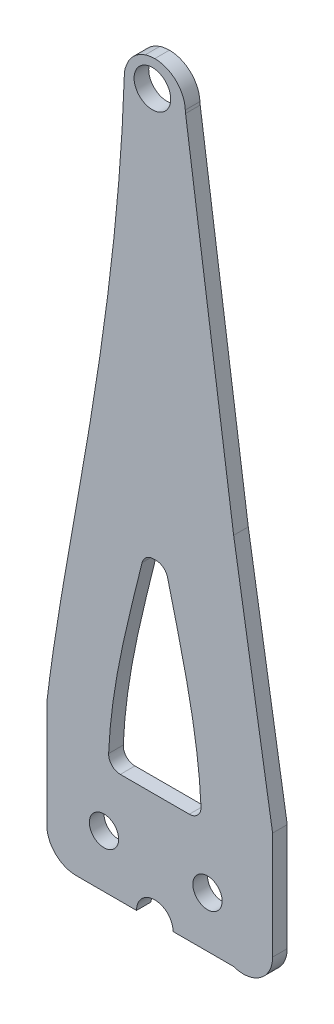
SolidWorks part; units mm, degrees
ref_plane "Front Plane" through (0, 0, 0) normal (0, 0, 1) x (1, 0, 0)
ref_plane "Top Plane" through (0, 0, 0) normal (0, 1, 0) x (1, 0, 0)
ref_plane "Right Plane" through (0, 0, 0) normal (1, 0, 0) x (0, 0, -1)
sketch "Sketch1" plane through (0, 0, 0) normal (0, 0, 1) x (1, 0, 0)
  line L0 (0, 2.6471) -> (0, -62.1483) construction
  line L1 (0, -62.1483) -> (-9.3726, -62.1483) construction
  line L3 (0, -29.7506) -> (-5.9944, -29.7506) construction
  line L4 (-6.8326, -62.1483) -> (6.8326, -62.1483)
  line L5 (-9.3726, -59.6083) -> (-9.3726, -50.4317)
  line L7 (10.218, -59.7531) -> (10.218, -50.4317)
  line L8 (0, -29.7506) -> (6.8398, -29.7506) construction
  line L9 (0, -29.7506) -> (0, -30.7704) construction
  line L13 (2.6678, -0.1469) -> (6.8398, -29.7506)
  line L14 (6.8398, -29.7506) -> (10.218, -50.4317)
  arc A0 (2.645, 0.1059) -> (0, 2.6471) centre (0, 0) ccw
  arc A1 (-2.6008, 0.493) -> (-2.6468, 0.0387) centre (0, 0) ccw
  arc A2 (-0.8377, 2.5111) -> (-2.217, 1.4464) centre (0, 0) ccw
  arc A3 (10.218, -59.7531) -> (6.8326, -62.1483) centre (7.678, -59.7531) cw
  arc A4 (-9.3726, -59.6083) -> (-6.8326, -62.1483) centre (-6.8326, -59.6083) ccw
  arc A5 (-2.6468, 0.0387) -> (-2.648, -0.0092) centre (-5.1866, 0.0758) cw
  arc A6 (2.645, 0.1059) -> (2.6678, -0.1469) centre (5.183, 0.2076) ccw
  spline S0 degree 2 poles (0, 2.6471) (-0.562, 2.6066) (-0.8377, 2.5111) knots 0 0 0 0.007249 0.007249 0.007249
  spline S1 degree 3 poles (-2.217, 1.4464) (-2.3484, 1.2496) (-2.5622, 0.7228) (-2.6008, 0.493) knots 0.022132 0.022132 0.022132 0.022132 0.030911 0.030911 0.030911 0.030911
  spline S2 degree 3 poles (-2.648, -0.0092) (-2.983, -10.0213) (-5.2117, -26.7487) (-8.559, -43.5813) (-9.3726, -50.4317) knots 0.035875 0.035875 0.035875 0.035875 0.412185 0.675163 0.675163 0.675163 0.675163
  point P13 (-9.3726, -48.7371)
  point P27 (2.6471, 0)
  dimension "D1" = 13.4112
  dimension "D2" = 2.54
  dimension "D3" = 2.54
  dimension "D4" = 64.7954
extrude "Boss-Extrude1" add sketch "Sketch1" along normal blind 1.27
sketch "Sketch2" plane through (0, 0, 1.27) normal (0, 0, 1) x (1, 0, 0)
  line L0 (-6.8326, -62.1483) -> (6.8326, -62.1483) construction
  line L1 (-1.5875, -62.1483) -> (1.5875, -62.1483)
  line L8 (6.8398, -29.7506) -> (2.6678, -0.1469)
  line L9 (10.218, -50.4317) -> (6.8398, -29.7506)
  line L10 (10.218, -59.7531) -> (10.218, -50.4317)
  line L11 (0, -52.6291) -> (-2.993, -52.6291)
  line L12 (0, -52.6291) -> (2.993, -52.6291)
  line L13 (0.1175, -35.0015) -> (-0.1175, -35.0015)
  line L14 (-6.8326, -62.1483) -> (6.8326, -62.1483)
  line L15 (-9.3726, -50.4317) -> (-9.3726, -59.6083)
  line L16 (6.8398, -29.7506) -> (2.6678, -0.1469)
  line L17 (10.218, -50.4317) -> (6.8398, -29.7506)
  line L18 (10.218, -59.7531) -> (10.218, -50.4317)
  line L19 (-6.8326, -62.1483) -> (6.8326, -62.1483)
  line L20 (-9.3726, -50.4317) -> (-9.3726, -59.6083)
  arc A1 (1.5875, -62.1483) -> (-1.5875, -62.1483) centre (0, -62.1483) ccw
  arc A6 (-4.0081, -51.5691) -> (-2.993, -52.6291) centre (-2.993, -51.6131) ccw
  arc A7 (4.0081, -51.5691) -> (2.993, -52.6291) centre (2.993, -51.6131) cw
  arc A8 (-1.1039, -35.7742) -> (-0.1175, -35.0015) centre (-0.1175, -36.0175) cw
  arc A9 (1.1039, -35.7742) -> (0.1175, -35.0015) centre (0.1175, -36.0175) ccw
  arc A18 (-0.8377, 2.5111) -> (-2.217, 1.4464) centre (0, 0) ccw
  arc A19 (2.645, 0.1059) -> (0, 2.6471) centre (0, 0) ccw
  arc A20 (2.645, 0.1059) -> (2.6678, -0.1469) centre (5.183, 0.2076) ccw
  arc A21 (6.8326, -62.1483) -> (10.218, -59.7531) centre (7.678, -59.7531) ccw
  arc A22 (-9.3726, -59.6083) -> (-6.8326, -62.1483) centre (-6.8326, -59.6083) ccw
  arc A23 (-2.648, -0.0092) -> (-2.6468, 0.0387) centre (-5.1866, 0.0758) ccw
  arc A24 (-2.6008, 0.493) -> (-2.6468, 0.0387) centre (0, 0) ccw
  arc A25 (-0.8377, 2.5111) -> (-2.217, 1.4464) centre (0, 0) ccw
  arc A26 (2.645, 0.1059) -> (0, 2.6471) centre (0, 0) ccw
  arc A27 (2.645, 0.1059) -> (2.6678, -0.1469) centre (5.183, 0.2076) ccw
  arc A28 (6.8326, -62.1483) -> (10.218, -59.7531) centre (7.678, -59.7531) ccw
  arc A29 (-9.3726, -59.6083) -> (-6.8326, -62.1483) centre (-6.8326, -59.6083) ccw
  arc A30 (-2.648, -0.0092) -> (-2.6468, 0.0387) centre (-5.1866, 0.0758) ccw
  arc A31 (-2.6008, 0.493) -> (-2.6468, 0.0387) centre (0, 0) ccw
  parabola Q1 (0, 2.6471) -> (-0.8377, 2.5111) focus (-1.0288, 2.2902) apex (-1.1006, 2.304)
  parabola Q2 (0, 2.6471) -> (-0.8377, 2.5111) focus (-1.0288, 2.2902) apex (-1.1006, 2.304)
  spline S0 degree 3 poles (4.0081, -51.5691) (3.9705, -50.701) (3.7622, -48.0392) (3.0647, -43.8926) (2.0396, -39.5173) (1.3828, -36.9054) (1.1039, -35.7742) knots 0.05904 0.05904 0.05904 0.05904 0.204248 0.505314 0.76084 0.955649 0.955649 0.955649 0.955649
  spline S1 degree 3 poles (-4.0081, -51.5691) (-3.9705, -50.701) (-3.7622, -48.0392) (-3.0647, -43.8926) (-2.0396, -39.5173) (-1.3828, -36.9054) (-1.1039, -35.7742) knots 0.05904 0.05904 0.05904 0.05904 0.204248 0.505314 0.76084 0.955649 0.955649 0.955649 0.955649
  spline S4 degree 3 poles (-1476.6625, -3716.7856) (1512.4522, 3733.2926) (-1547.1703, -3719.0692) (1561.2797, 3682.003) knots -0.132423 -0.132423 -0.132423 -0.132423 0.185405 0.185405 0.185405 0.185405 only from (-2.217, 1.4464) to (-2.6008, 0.493)
  spline S5 degree 3 poles (-3643.9579, 1617.3465) (-68.9353, 311.6588) (89.2381, 32.1062) (-108.0056, -280.8735) (3977.13, 99.6884) knots -6.309162 -6.309162 -6.309162 -6.309162 0.412185 5.086135 5.086135 5.086135 5.086135 only from (-2.648, -0.0092) to (-9.3726, -50.4317)
  spline S6 degree 3 poles (-2.217, 1.4464) (-2.3484, 1.2496) (-2.5622, 0.7228) (-2.6008, 0.493) knots 0.022132 0.022132 0.022132 0.022132 0.030911 0.030911 0.030911 0.030911
  spline S7 degree 3 poles (-2.648, -0.0092) (-2.983, -10.0213) (-5.2117, -26.7487) (-8.559, -43.5813) (-9.3726, -50.4317) knots 0.035875 0.035875 0.035875 0.035875 0.412185 0.675163 0.675163 0.675163 0.675163
  dimension "D1" = 0
  dimension "D2" = 1.5875
extrude "Cut-Extrude2" cut sketch "Sketch2" against normal through all contours S1 A6 L11 L12 A7 S0 A9 L13 A8 | A1 L1 region at (0, -45.5237, 1.27)
sketch "Sketch4" plane through (0, 0, 0) normal (0, 0, -1) x (-1, 0, 0)
  circle A0 centre (4.4075, -57.577) radius 1.27 construction
  circle A1 centre (-4.5713, -57.7408) radius 1.27 construction
  circle A2 centre (0.21, 0.2873) radius 1.5875 construction
  circle A3 centre (4.4075, -57.577) radius 1.27
  circle A4 centre (-4.5713, -57.7408) radius 1.27
  circle A5 centre (0.21, 0.2873) radius 1.5875
extrude "Cut-Extrude3" cut sketch "Sketch4" against normal through all
equation "\"HOLE SIZE\"= .125"
